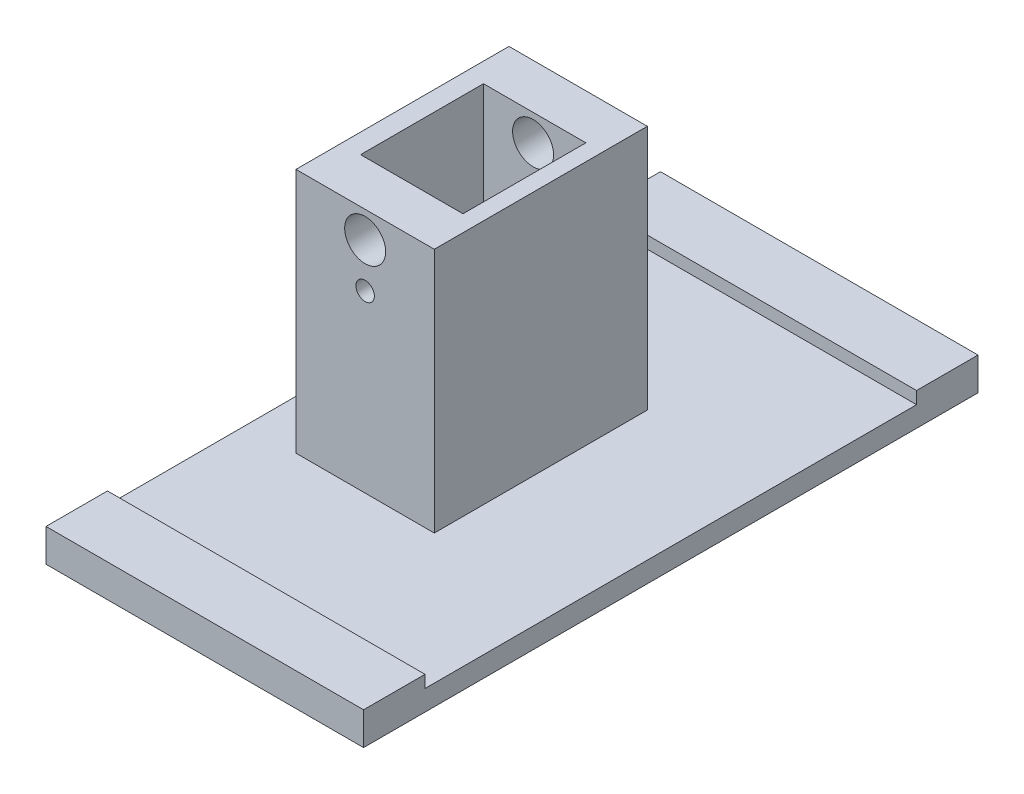
SolidWorks part; units mm, degrees
ref_plane "Front Plane" through (0, 0, 0) normal (0, 0, 1) x (1, 0, 0)
ref_plane "Top Plane" through (0, 0, 0) normal (0, 1, 0) x (1, 0, 0)
ref_plane "Right Plane" through (0, 0, 0) normal (1, 0, 0) x (0, 0, -1)
sketch "Sketch2" plane through (0, 0, 0) normal (0, 1, 0) x (1, 0, 0)
  line L0 (0, 38.1) -> (39.3827, 38.1) construction
  line L1 (0, 0) -> (39.3827, 0)
  line L2 (0, 0) -> (0, 76.2)
  line L3 (0, 76.2) -> (39.3827, 76.2)
  line L4 (39.3827, 0) -> (39.3827, 76.2)
  line L5 (23.9719, 38.1) -> (23.9719, 53.467) construction
  line L6 (23.9719, 38.1) -> (23.9719, 22.733) construction
  line L7 (39.3827, 68.58) -> (0, 68.58)
  line L8 (8.5334, 38.1) -> (8.5334, 30.48)
  line L9 (8.5334, 30.48) -> (21.2334, 30.48)
  line L10 (8.5334, 38.1) -> (8.5334, 45.72)
  line L11 (8.5334, 45.72) -> (21.2334, 45.72)
  line L12 (21.2334, 45.72) -> (21.2334, 30.48)
  line L13 (33.1404, 76.2) -> (33.1404, 68.58) construction
  line L14 (28.6413, 0) -> (28.6413, 7.62) construction
  line L15 (39.3827, 7.62) -> (0, 7.62)
  line L16 (6.1079, 38.1) -> (6.1079, 24.892)
  line L17 (6.1079, 24.892) -> (23.2654, 24.892)
  line L18 (6.1079, 38.1) -> (6.1079, 51.308)
  line L19 (6.1079, 51.308) -> (23.2654, 51.308)
  line L20 (23.2654, 51.308) -> (23.2654, 24.892)
  line L26 (8.5334, 27.432) -> (8.5334, 30.48)
  arc A2 (0, 41.91) -> (0, 34.29) centre (0, 38.1) cw
  dimension "D1" = 5.588
  dimension "D2" = 15.24
  dimension "D3" = 39.3827
extrude "Boss-Extrude2" add sketch "Sketch2" along normal blind 4.064 contours L4 L15 L2 L1 | L7 L4 L3 L2 region at (19.6913, 0, -3.81) region at (19.6913, 0, -72.39)
extrude "Boss-Extrude3" add sketch "Sketch2<3>" along normal blind 2.54 contours L15 L4 L7 L2 | L20 L19 L18 L16 L17 L11 L12 L9 L8 L10 | L12 L11 L10 L8 L9 | L26 L9 | L11 region at (0.7257, 0, -20.955) region at (14.8834, 0, -38.1) region at (6.4228, 0, -44.704)
sketch "Sketch2<3>" plane through (0, 0, 0) normal (0, 1, 0) x (1, 0, 0) same geometry as "Sketch2"
extrude "Boss-Extrude4" add sketch "Sketch2<8>" along normal blind 33.02 contours L20 L19 L18 L16 L17 L26 L8 L10 L12 | L11 | L26 L9 region at (6.4228, 0, -44.704)
sketch "Sketch2<8>" plane through (0, 0, 0) normal (0, 1, 0) x (1, 0, 0) same geometry as "Sketch2"
sketch "Sketch4" plane through (0, 2.54, 0) normal (0, 1, 0) x (1, 0, 0)
  line L0 (21.2334, 45.72) -> (8.5334, 45.72)
  line L1 (8.5334, 45.72) -> (8.5334, 48.26)
  line L2 (8.5334, 48.26) -> (21.2334, 48.26)
  line L3 (21.2334, 48.26) -> (21.2334, 45.72)
  line L4 (8.5334, 30.48) -> (21.2334, 30.48)
  line L5 (21.2334, 30.48) -> (21.2334, 27.94)
  line L6 (21.2334, 27.94) -> (8.5334, 27.94)
  line L7 (8.5334, 27.94) -> (8.5334, 30.48)
extrude "Cut-Extrude2" cut sketch "Sketch4" along normal blind 17.78
sketch "Sketch5" plane through (0, 0, -51.308) normal (0, 0, -1) x (-1, 0, 0)
  line L0 (-23.2654, 29.718) -> (-6.1079, 29.718) construction
  line L1 (-23.2654, 33.02) -> (-23.2654, 2.54) construction
  line L2 (-6.1079, 33.02) -> (-6.1079, 2.54) construction
  line L3 (-14.6866, 29.718) -> (-14.6866, 24.257) construction
  line L4 (-23.2654, 33.02) -> (-6.1079, 33.02) construction
  circle A0 centre (-14.6866, 29.718) radius 2.54
  circle A1 centre (-14.6866, 24.257) radius 1.143
  dimension "D1" = 3.302
extrude "Cut-Extrude3" cut sketch "Sketch5" against normal up to surface (26.416 mm away) up to face at (14.6866, 17.78, -24.892)
sketch "Sketch6" plane through (0, 33.02, 0) normal (0, 1, 0) x (1, 0, 0)
  line L0 (21.4874, 24.892) -> (21.4874, 26.67) construction
  line L1 (6.1079, 24.892) -> (23.2654, 24.892) construction
  line L2 (21.4874, 26.67) -> (23.2654, 26.67) construction
  line L3 (23.2654, 51.308) -> (23.2654, 24.892) construction
  line L4 (23.2654, 26.67) -> (23.2654, 24.892)
  line L5 (23.2654, 24.892) -> (21.4874, 24.892)
  arc A0 (23.2654, 26.67) -> (21.4874, 24.892) centre (21.4874, 26.67) cw
